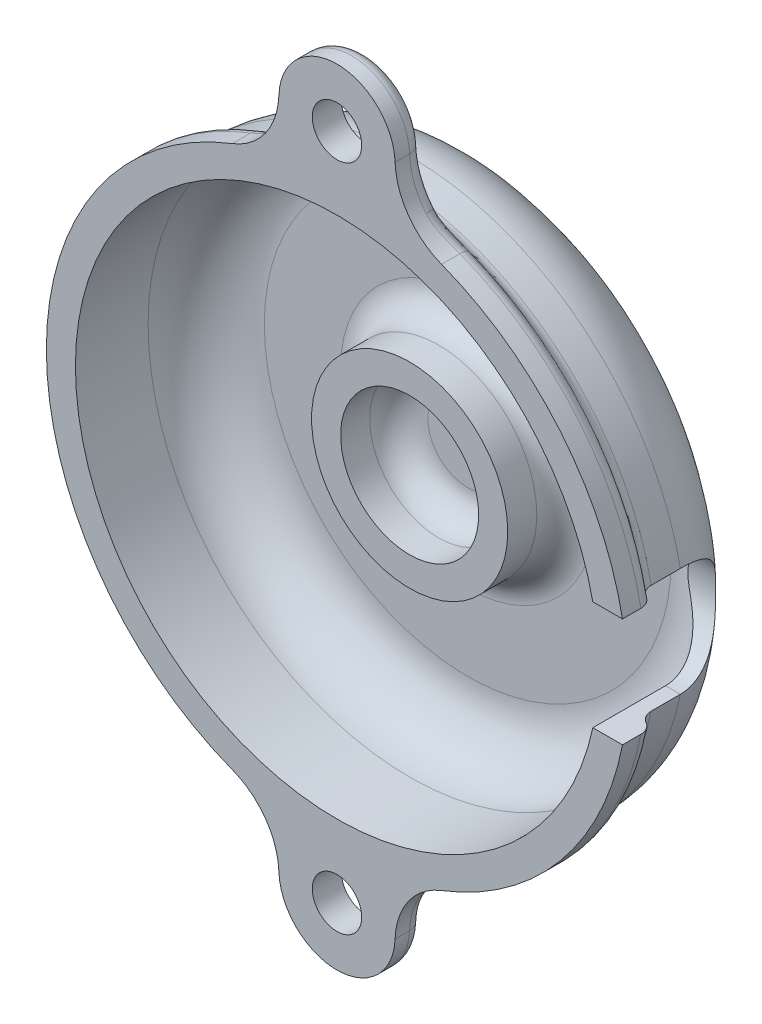
SolidWorks part; units mm, degrees
ref_plane "Спереди" through (0, 0, 0) normal (0, 0, 1) x (1, 0, 0)
ref_plane "Сверху" through (0, 0, 0) normal (0, 1, 0) x (1, 0, 0)
ref_plane "Справа" through (0, 0, 0) normal (1, 0, 0) x (0, 0, -1)
sketch "Эскиз1" plane through (0, 0, 0) normal (0, 0, 1) x (1, 0, 0)
  arc A0 (2.4625, -19.8478) -> (2.4625, 19.8478) centre (0, 0) ccw
  arc A1 (2.4625, 19.8478) -> (-2.4625, 19.8478) centre (0, 23) ccw
  circle A2 centre (0, 23) radius 1.7
  circle A3 centre (0, -23) radius 1.7
  arc A4 (-2.4625, -19.8478) -> (2.4625, -19.8478) centre (0, -23) ccw
  arc A5 (-2.4625, 19.8478) -> (-2.4625, -19.8478) centre (0, 0) ccw
  circle A9 centre (0, 0) radius 23 construction
  point P14 (0, 0)
  point P17 (0, 0)
  dimension "D1" = 40
  dimension "D2" = 3.4
  dimension "D3" = 8
  dimension "D5" = 46
  dimension "D4" = 2
extrude "основание" add sketch "Эскиз1" along normal blind 2
sketch "Эскиз2" plane through (0, 0, 0) normal (0, 0, -1) x (-1, 0, 0)
  circle A0 centre (0, 0) radius 19
extrude "место для энкодера" [suppressed] add sketch "Эскиз2" along normal blind 14
sketch "Эскиз3" plane through (0, 0, 2) normal (0, 0, 1) x (1, 0, 0)
  circle A0 centre (0, 0) radius 18
  dimension "D1" = 36
extrude "углубление для двигателя" [suppressed] cut sketch "Эскиз3" against normal blind 14
chamfer "Фаска1" [suppressed] distance 1 distance2 20
fillet "Скругление4" [suppressed] radius 5
fillet "Скругление5" [suppressed] radius 2
extrude "Место под выступ двигателя с проводами" add sketch "Эскиз2<2>" along normal blind 8
sketch "Эскиз2<2>" plane through (0, 0, 0) normal (0, 0, -1) x (-1, 0, 0) same geometry as "Эскиз2"
fillet "Скругления наплывов" radius 5 4 edges at (-2.4625, -19.8478, 1) (2.4625, -19.8478, 1) (2.4625, 19.8478, 1) (-2.4625, 19.8478, 1)
fillet "Скругление10" radius 5 1 edges at (-19, 0, -8)
fillet "Скругление11" radius 1 1 edges at (-19, 0, 0)
fillet "Скругление12" radius 1 8 edges at (0, 27, 0) (-4.9233, 20.4229, 0) (4.9233, 20.4229, 0) (20, 0, 0) (4.9233, -20.4229, 0) (0, -27, 0) (-4.9233, -20.4229, 0) (-20, 0, 0)
sketch "Эскиз14" plane through (0, 0, 0) normal (1, 0, 0) x (0, 0, -1)
  line L0 (-2, 18) -> (3, 18)
  line L2 (7, 14) -> (7, 0)
  line L3 (-2, 18) -> (-2, 0)
  line L4 (-2, 0) -> (0, 0) construction
  line L5 (7, 0) -> (-2, 0)
  line L6 (-2, 18.6609) -> (-2, -18.6609) construction
  arc A0 (7, 14) -> (3, 18) centre (3, 14) ccw
  arc A1 (8, 14) -> (3, 19) centre (3, 14) ccw construction
  dimension "D1" = 18
revolve "Углубление под двигатель jgb37_3525" cut sketch "Эскиз14" angle 360 about L4
sketch "Эскиз12" plane through (0, 0, -7) normal (0, 0, -1) x (-1, 0, 0)
  circle A0 centre (0, 0) radius 4.75
  circle A1 centre (0, 0) radius 6.75
  dimension "D1" = 9.5
  dimension "D2" = 2
extrude "защита проводов от вращающегося вала" add sketch "Эскиз12" against normal offset from surface (4 mm away) 5 up to face at (18, 0, 2)
ref_plane "Плоскость под пазпод провода для защиты 3525" through (0, 0, 0) normal (1, 0, 0) x (0, 0, 1)
sketch "Эскиз13" plane through (0, 0, 0) normal (1, 0, 0) x (0, 0, 1)
  line L0 (-3, 3.75) -> (2, 3.75)
  line L2 (-3, 0) -> (2, 0) construction
  line L3 (-3, -3.75) -> (2, -3.75)
  line L4 (-8, 14) -> (-8, -14) construction
  line L9 (2, 3.75) -> (2, -3.75)
  line L10 (2, -18.6609) -> (2, 18.6609) construction
  arc A0 (-3, 3.75) -> (-3, -3.75) centre (-3, 0) ccw
  dimension "D1" = 3.75
  dimension "D2" = 5
extrude "Паз под провода двигателя jgb37_3525" cut sketch "Эскиз13" along normal up to next from offset 15
chamfer "Фаски под шляпки" [suppressed] distance 1.5 angle 45
ref_plane "Плоскость паза под провода" [suppressed] through (0, 0, 0) normal (-0.866, 0.5, 0) x (0, 0, 1)
sketch "Эскиз9" [suppressed] plane through (0, 0, 0) normal (-0.866, 0.5, 0) x (0.5, 0.866, 0)
  line L0 (0, 0) -> (0, 14) construction
  line L1 (14.5438, 14) -> (-14.5438, 14) construction
  circle A0 centre (0, 8) radius 3.65
  dimension "D1" = 7.3
  dimension "D2" = 6
extrude "паз для проводов" [suppressed] cut sketch "Эскиз9" along normal through all
fillet "Скругление7" [suppressed] radius 0.5
ref_plane "Плоскость1" [suppressed] through (0, 0, 0) normal (0.8192, -0.5736, 0) x (0, 0, 1)
sketch "Эскиз10" [suppressed] plane through (0, 0, 0) normal (0.8192, -0.5736, 0) x (0, 0, 1)
  line L0 (-10, 0) -> (2, 0) construction
  line L2 (-8, 3) -> (2, 3)
  line L3 (2, 3) -> (2, -3)
  line L4 (2, -11.1561) -> (2, 13.869) construction
  line L5 (2, -3) -> (-8, -3)
  line L6 (-14, 19.3) -> (-14, -19.3) construction
  arc A0 (-8, 3) -> (-8, -3) centre (-8, 0) ccw
  dimension "D1" = 6
  dimension "D2" = 6
extrude "Паз для проводов версия 2" [suppressed] cut sketch "Эскиз10" against normal through all
sketch "Эскиз11" [suppressed] plane through (0, 0, -14) normal (0, 0, -1) x (-1, 0, 0)
  circle A0 centre (0, 0) radius 40.0759
extrude "Вырез-Вытянуть1" [suppressed] cut sketch "Эскиз11" against normal blind 14
fillet "Скругление8" [suppressed] radius 5
fillet "Скругление13" radius 2 2 edges at (-4.75, 0, -7) (6.75, 0, -7)
